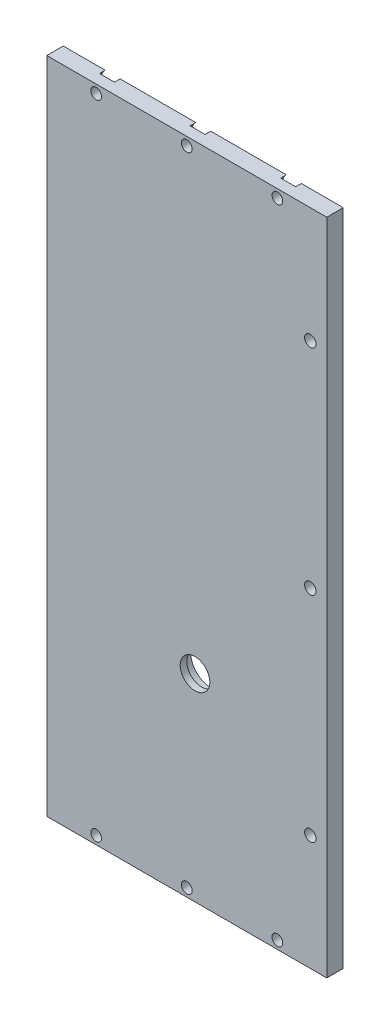
SolidWorks part; units mm, degrees
ref_plane "Front Plane" through (0, 0, 0) normal (0, 0, 1) x (1, 0, 0)
ref_plane "Top Plane" through (0, 0, 0) normal (0, 1, 0) x (1, 0, 0)
ref_plane "Right Plane" through (0, 0, 0) normal (1, 0, 0) x (0, 0, -1)
sketch "Sketch1" plane through (0, 0, 0) normal (0, 0, 1) x (1, 0, 0)
  line L1 (-158.3632, 91.8414) -> (-73.3632, 91.8414)
  line L2 (-158.3632, 91.8414) -> (-158.3632, -108.1586)
  line L3 (-158.3632, -108.1586) -> (-73.3632, -108.1586)
  line L4 (-73.3632, 91.8414) -> (-73.3632, -108.1586)
  dimension "D1" = 200
  dimension "D2" = 85
extrude "Boss-Extrude1" add sketch "Sketch1" along normal blind 5
sketch "Sketch4" plane through (0, 0, 0) normal (0, 0, -1) x (-1, 0, 0)
  line L0 (73.3632, -8.1586) -> (158.3632, -8.1586)
  line L1 (73.3632, -108.1586) -> (73.3632, 91.8414) construction
  line L2 (158.3632, 91.8414) -> (158.3632, -108.1586) construction
  line L3 (78.3632, -73.1586) -> (78.3632, 56.8414)
  line L4 (73.3632, -108.1586) -> (73.3632, 91.8414) construction
  point P9 (78.3632, -8.1586)
  dimension "D1" = 130
  dimension "D2" = 5
hole_wizard "CBORE for #4 Binding Head Machine Screw1" positions "Sketch5" profile "Sketch6" counterbore size "#4" standard "ANSI Inch" end condition through all
sketch "Sketch5" plane through (0, 0, 0) normal (0, 0, -1) x (-1, 0, 0)
  line L0 (78.3632, -73.1586) -> (78.3632, 56.8414) construction
  point P0 (78.3632, 56.8414)
  point P3 (78.3632, -8.1586)
  point P7 (78.3632, -73.1586)
sketch "Sketch6" plane through (-78.3632, 56.8414, 0) normal (1, 0, 0) x (0, 1, 0)
  line L0 (0, 0) -> (0, 5)
  line L1 (0, 5) -> (1.7272, 5)
  line L3 (1.7272, 5) -> (1.7272, 1.7272)
  line L4 (1.7272, 1.7272) -> (3.3731, 1.7272)
  line L5 (3.3731, 1.7272) -> (3.3731, 0)
  line L7 (3.3731, 0) -> (0, 0)
  line L11 (0, -6.35) -> (0, 107.95) construction
  dimension "Thru Hole Dia." = 3.4544
  dimension "Thru Hole Depth" = 5
  dimension "C'Bore Dia." = 6.7462
  dimension "C'Bore Depth" = 1.7272
sketch "Sketch7" plane through (0, 0, 0) normal (0, 0, -1) x (-1, 0, 0)
  line L0 (88.3632, -105.6586) -> (143.3632, -105.6586)
  line L1 (158.3632, -108.1586) -> (73.3632, -108.1586) construction
  line L2 (73.3632, -108.1586) -> (73.3632, 91.8414) construction
  line L3 (73.3632, -8.1586) -> (158.3632, -8.1586)
  line L4 (88.3632, 89.3414) -> (143.3632, 89.3414)
  point P3 (115.8632, -105.6586)
  point P7 (115.8632, -108.1586)
  dimension "D1" = 2.5
  dimension "D2" = 15
  dimension "D3" = 0
hole_wizard "CBORE for #4 Binding Head Machine Screw2" positions "Sketch8" profile "Sketch9" counterbore size "#4" standard "ANSI Inch" end condition up to next
sketch "Sketch8" plane through (0, 0, 0) normal (0, 0, -1) x (-1, 0, 0)
  line L0 (88.3632, 89.3414) -> (143.3632, 89.3414) construction
  line L1 (88.3632, -105.6586) -> (143.3632, -105.6586) construction
  point P0 (88.3632, 89.3414)
  point P3 (115.8632, 89.3414)
  point P7 (143.3632, 89.3414)
  point P10 (143.3632, -105.6586)
  point P13 (115.8632, -105.6586)
  point P17 (88.3632, -105.6586)
sketch "Sketch9" plane through (-88.3632, 89.3414, 0) normal (1, 0, 0) x (0, 1, 0)
  line L0 (0, 0) -> (0, 5)
  line L1 (0, 5) -> (1.6319, 5)
  line L3 (1.6319, 5) -> (1.632, 1.7272)
  line L4 (1.632, 1.7272) -> (3.3731, 1.7272)
  line L5 (3.3731, 1.7272) -> (3.3731, 0)
  line L7 (3.3731, 0) -> (0, 0)
  line L11 (0, -6.35) -> (0, 107.95) construction
  dimension "Thru Hole Dia." = 3.2639
  dimension "Thru Hole Depth" = 5
  dimension "C'Bore Dia." = 6.7462
  dimension "C'Bore Depth" = 1.7272
sketch "Sketch10" plane through (0, 0, 0) normal (0, 0, -1) x (-1, 0, 0)
  line L1 (73.3632, -108.1586) -> (73.3632, 91.8414) construction
  line L2 (73.3632, -8.1586) -> (158.3632, -8.1586) construction
  circle A0 centre (113.3632, -48.1586) radius 6.35
  circle A1 centre (113.3632, -48.1586) radius 4.5
  dimension "D2" = 12.7
  dimension "D4" = 9
  dimension "D1" = 40
  dimension "D3" = 40
sketch "Sketch11" plane through (-158.3632, 0, 0) normal (-1, 0, 0) x (0, 0, 1)
  line L0 (2.5, 91.8414) -> (2.5, -108.1586)
  line L1 (5, 91.8414) -> (0, 91.8414) construction
  line L2 (5, -108.1586) -> (0, -108.1586) construction
  line L3 (0, -8.1586) -> (5, -8.1586)
  line L4 (5, 91.8414) -> (5, -108.1586) construction
  point P11 (2.5, 41.8414)
  point P12 (2.5, -58.1586)
  dimension "D1" = 50
hole_wizard "#4-40 Tapped Hole2" positions "Sketch14" profile "Sketch15" tap size "#4-40" standard "ANSI Inch"
sketch "Sketch14" plane through (-158.3632, 0, 0) normal (-1, 0, 0) x (0, 0, 1)
  point P0 (2.5, -58.1586)
  point P3 (2.5, 41.8414)
sketch "Sketch15" plane through (-158.3632, -58.1586, 2.5) normal (0, 1, 0) x (0, 0, 1)
  line L0 (0, 0) -> (0, 8.2792)
  line L1 (0, 8.2792) -> (1.1303, 7.6)
  line L2 (1.1303, 7.6) -> (1.1303, 0)
  line L5 (1.1303, 0) -> (0, 0)
  line L10 (0, 8.2792) -> (-1.1303, 7.6) construction
  line L11 (0, -6.35) -> (0, 107.95) construction
  dimension "Tap Drill Dia." = 2.2606
  dimension "Tap Drill Depth" = 7.6
  dimension "Drill Angle" = 118
cosmetic thread "Hole Thread3" parameters "D1"=5.69, "D2"=2.8448
cosmetic thread "Hole Thread4" parameters "D1"=5.69, "D2"=2.8448
extrude "Cut-Extrude2" cut sketch "Sketch10" against normal through all contours A1
extrude "Cut-Extrude3" cut sketch "Sketch10<6>" against normal offset from surface (3 mm away) 2 contours A0 up to face at (-117.8632, -48.1586, 5)
sketch "Sketch10<6>" plane through (0, 0, 0) normal (0, 0, -1) x (-1, 0, 0) same geometry as "Sketch10"
